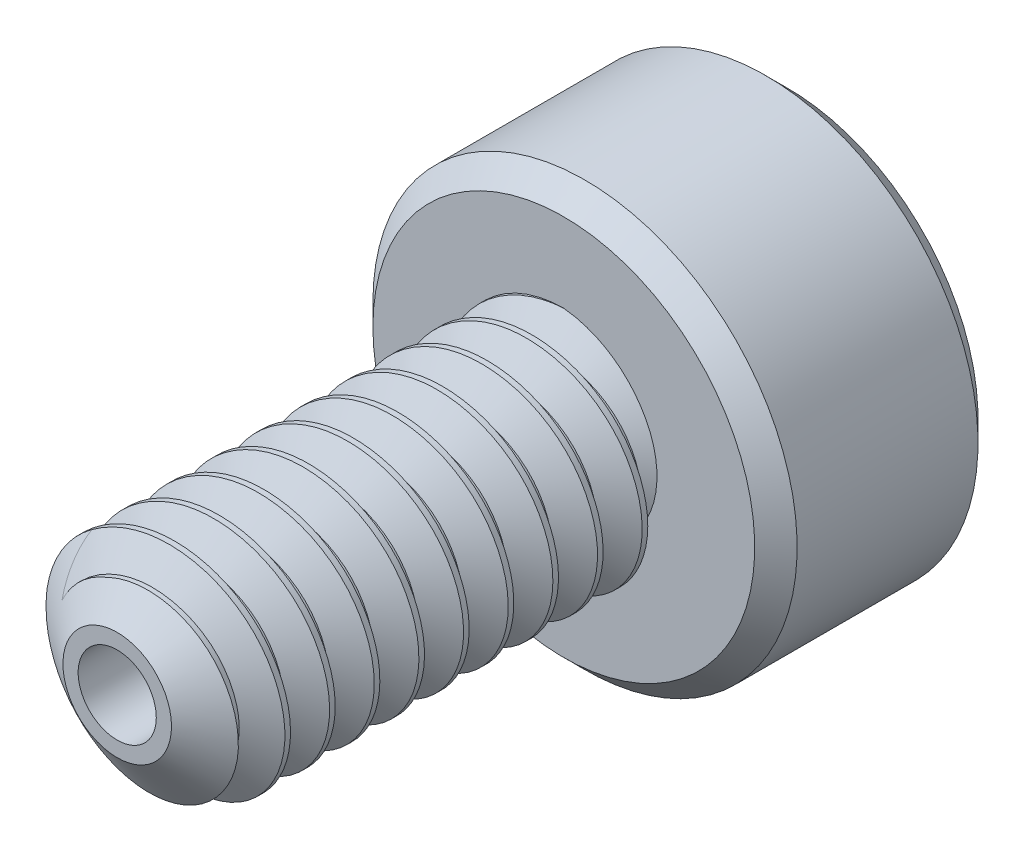
SolidWorks part; units mm, degrees
other "DetailItem1"
ref_plane "Front Plane" through (0, 0, 0) normal (0, 0, 1) x (1, 0, 0)
ref_plane "Top Plane" through (0, 0, 0) normal (0, 1, 0) x (1, 0, 0)
ref_plane "Right Plane" through (0, 0, 0) normal (1, 0, 0) x (0, 0, -1)
sketch "Sketch1" plane through (0, 0, 0) normal (0, 0, 1) x (1, 0, 0)
  circle A0 centre (0, 0) radius 1
  dimension "OD" = 2
extrude "Extrude1" add sketch "Sketch1" against normal blind 4
sketch "Sketch2" plane through (0, 0, 0) normal (0, 0, 1) x (1, 0, 0)
  circle A0 centre (0, 0) radius 1 construction
  circle A1 centre (0, 0) radius 1
curve "Helix/Spiral1" pitch 0.4 height 4.4 radius 1 centre (0, 0, 0) axis (0, 0, -1) start towards (0, 1, 0) parameters "pitch"=0.4
sketch "Sketch3" plane through (0, 0, 0) normal (1, 0, 0) x (0, 0, -1)
  line L0 (-0.35, 1) -> (-0.2, 0.7402)
  line L1 (-0.2, 0.7402) -> (-0.15, 0.7402)
  line L2 (-0.15, 0.7402) -> (0, 1)
  line L3 (-0.35, 1) -> (0, 1)
  line L4 (-0.175, 1) -> (-0.175, 0.7402) construction
  line L5 (-0.275, 0.8701) -> (-0.075, 0.8701) construction
  line L6 (0, 1) -> (0, -1) construction
  dimension "D1" = 0.05
  dimension "D2" = 0.2
  dimension "D3" = 60
sweep "Cut-Sweep1" cut profiles "Sketch3" path "Helix/Spiral1"
sketch "Sketch4" plane through (0, 0, 0) normal (1, 0, 0) x (0, 0, -1)
  line L0 (0.3598, 1) -> (0, 0.4862)
  line L1 (0, 0.4862) -> (0, 1)
  line L2 (0.3598, 1) -> (0, 1)
  line L3 (-0.35, 1) -> (0, 1) construction
  line L4 (0, 0) -> (7.0209, 0) construction
  dimension "D1" = 55
  dimension "D2" = 0.254
revolve "Cut-Revolve1" cut sketch "Sketch4" angle 360 about L4
sketch "Sketch6" plane through (0, 0, -4) normal (0, 0, -1) x (-1, 0, 0)
  circle A0 centre (0, 0) radius 1.9
  dimension "head dia" = 3.8
extrude "Extrude2" add sketch "Sketch6" along normal blind 2
sketch "Sketch7" plane through (0, 0, -6) normal (0, 0, -1) x (-1, 0, 0)
  line L1 (0, 0.866) -> (-0.75, 0.433)
  line L2 (-0.75, 0.433) -> (-0.75, -0.433)
  line L3 (-0.75, -0.433) -> (0, -0.866)
  line L4 (0, -0.866) -> (0.75, -0.433)
  line L5 (0.75, -0.433) -> (0.75, 0.433)
  line L6 (0.75, 0.433) -> (0, 0.866)
  circle A0 centre (0, 0) radius 0.75 construction
  dimension "hex dia" = 1.5
extrude "Cut-Extrude1" cut sketch "Sketch7" against normal blind 1.125
sketch "Sketch8" plane through (0, 0, -6) normal (0, 0, -1) x (-1, 0, 0)
  circle A0 centre (0, 0) radius 0.866
extrude "Cut-Extrude2" cut sketch "Sketch8" against normal through all draft 45
chamfer "Chamfer1" distance 0.19 angle 45 2 edges at (-1.9, 0, -6) (-1.9, 0, -4)
sketch "Sketch10" plane through (0, 0, -4) normal (0, 0, 1) x (1, 0, 0)
  circle A1 centre (0, 0) radius 1
  circle A2 centre (0, 0) radius 1
  dimension "D1" = 0
ref_plane "Plane1" through (0, 0, 0) normal (0, 0, 1) x (1, 0, 0)
extrude "partial thread" [suppressed] add sketch "Sketch10" along normal up to surface (12.7 mm away) separate body up to plane "Plane1"
chamfer "Chamfer2" [suppressed] distance 0.04 angle 45
combine bodies "Combine1" [suppressed] operation type add bodies to combine 107 108
sketch "Sketch9" plane through (0, 0, 0) normal (1, 0, 0) x (0, 0, -1)
  line L0 (0, 1) -> (0, -1) construction
  line L1 (1, 1) -> (1, -1) construction
  dimension "D1" = 1
sketch "Sketch11" plane through (0, 0, 0) normal (0, 0, 1) x (1, 0, 0)
  circle A0 centre (0, 0) radius 0.35
  dimension "Vent Dia" = 0.7
extrude "Cut-Extrude3" cut sketch "Sketch11" against normal through all
equation "\"D3@Helix/Spiral1\" = \"screw length@Extrude1\"+\"pitch@Helix/Spiral1\""
equation "\"D1@Sketch3\" = \"pitch@Helix/Spiral1\"*.125"
equation "\"D2@Sketch3\" = \"pitch@Helix/Spiral1\"*.5"
equation "\"D1@Cut-Extrude1\" = \"hex dia@Sketch7\"*.75"
equation "\"D1@Chamfer1\" = \"head dia@Sketch6\"*.05"
equation "\"D1@Sketch9\" = \"pitch@Helix/Spiral1\"*2.5"
equation "\"D1@Chamfer2\"=\"OD@Sketch1\"*.02"
